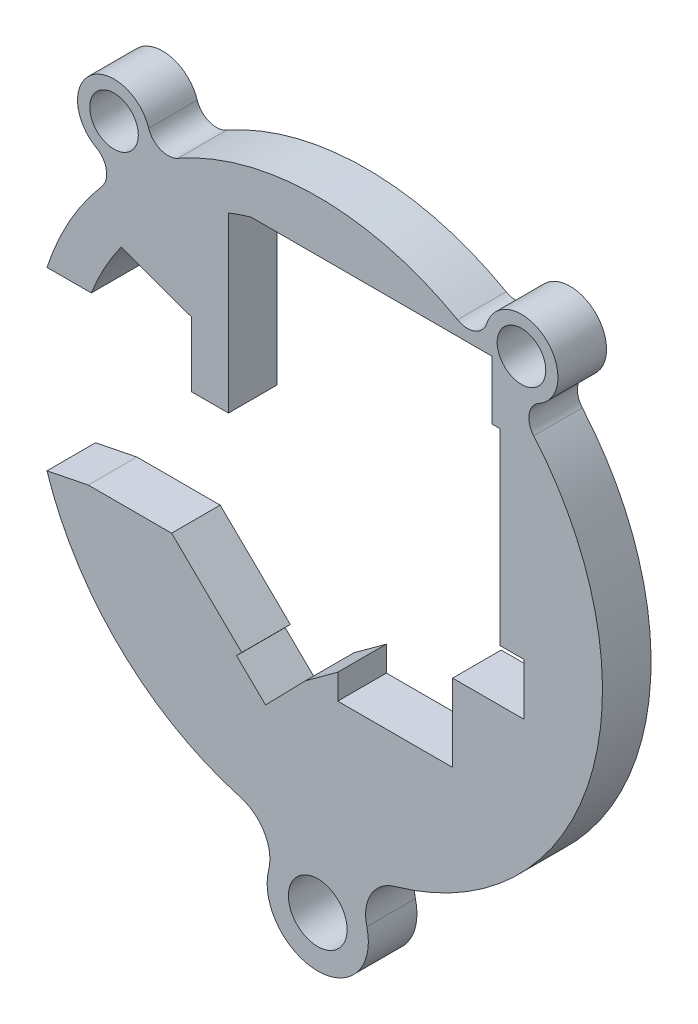
SolidWorks part; units mm, degrees
ref_plane "Front Plane" through (0, 0, 0) normal (0, 0, 1) x (1, 0, 0)
ref_plane "Top Plane" through (0, 0, 0) normal (0, 1, 0) x (1, 0, 0)
ref_plane "Right Plane" through (0, 0, 0) normal (1, 0, 0) x (0, 0, -1)
sketch "Sketch1" plane through (0, 0, 0) normal (0, 0, 1) x (1, 0, 0)
  line L1 (-14.9521, -2.9485) -> (-16.9841, -2.9485)
  line L2 (-16.9841, 2.9485) -> (-16.9841, 5.5245)
  line L3 (-14.9521, 2.9485) -> (-16.9841, 2.9485)
  line L4 (-16.9841, 5.5245) -> (-21.1739, 5.5245)
  line L5 (-16.9841, -2.9485) -> (-16.9841, -5.5245)
  line L6 (-16.9841, -5.5245) -> (-20.8712, -5.5245)
  line L7 (-15.24, 0) -> (-21.59, 0) construction
  line B0 (-15.24, 18.2372) -> (15.24, 18.2372)
  line B1 (11.43, 14.6558) -> (11.43, -0.8128)
  line B2 (0, 18.2372) -> (0, 0) construction
  line B3 (-5.6007, 14.1736) -> (-5.6007, -0.8128)
  line B4 (11.43, 14.6558) -> (-4.1791, 14.6558)
  line B5 (-5.6007, -0.8128) -> (11.43, -0.8128)
  line B6 (8.4582, -4.064) -> (12.9413, -4.064)
  line B7 (11.43, -0.8128) -> (12.9413, -0.8128)
  line B8 (12.9413, -0.8128) -> (12.9413, -4.064)
  line B9 (8.4582, -7.3406) -> (1.2573, -7.3406)
  line B10 (8.4582, -4.064) -> (8.4582, -7.3406)
  line B11 (-4.3942, -0.8128) -> (-4.3942, -4.064)
  line B12 (-4.3942, -4.064) -> (1.2573, -4.064)
  line B13 (1.2573, -4.064) -> (1.2573, -7.3406)
  line B14 (-0.7747, -8.8265) -> (-3.2737, -11.3919)
  line B15 (-0.7747, -8.8265) -> (-2.5941, -7.0541)
  line B16 (-2.5941, -7.0541) -> (-2.9176, -7.3862)
  line B17 (-2.9176, -7.3862) -> (-8.5123, -1.9362)
  line B18 (-8.5123, -1.9362) -> (-10.3645, -3.8375)
  line B19 (-10.3645, -3.8375) -> (-4.7697, -9.2875)
  line B20 (-4.7697, -9.2875) -> (-5.0932, -9.6195)
  line B21 (-5.0932, -9.6195) -> (-3.2737, -11.3919)
  line B22 (-12.3326, 18.2372) -> (-12.3326, 8.9535)
  line B23 (-7.9248, 18.2372) -> (-7.9248, 7.366) construction
  line B24 (-12.3326, 8.9535) -> (-7.9248, 7.366)
  line B25 (-5.6007, 3.302) -> (-7.9248, 3.302)
  line B26 (-7.9248, 3.302) -> (-7.9248, 7.366)
  line B27 (-14.3951, -5.0038) -> (-9.1672, -5.0038)
  line B28 (-0.7747, -8.8265) -> (1.2573, -7.3406)
  arc B29 (-3.302, 14.878) -> (3.302, 14.878) centre (0, 0) ccw
  circle B30 centre (0, -18.415) radius 1.4224
  circle B31 centre (0, 18.415) radius 1.4224
  circle B32 centre (0, 0) radius 21.59
  line B33 (1.2573, -8.9154) -> (8.4582, -8.9154)
  line B34 (1.2573, -7.3406) -> (1.2573, -8.9154)
  line B35 (8.4582, -7.3406) -> (8.4582, -8.9154)
  dimension "D1" = 2.032
  dimension "D2" = 11.049
sketch_block_instance "Block1-1"
sketch_block "Block1" parameters "D1"=3.81, "D2"=30.48, "D3"=3.5814, "D4"=9.6393, "D5"=19.05, "D6"=22.3012, "D7"=1.5113, "D8"=4.4831, "D9"=6.5278, "D10"=7.2009, "D11"=5.6515, "D12"=27.0637, "D13"=29.6291, "D14"=3.5814, "D15"=14.4653, "D16"=2.54, "D17"=2.6543, "D18"=10.3505, "D19"=9.2837, "D20"=10.8712, "D21"=7.3152, "D22"=14.9352, "D23"=23.241
extrude "Boss-Extrude1" add sketch "Sketch1" along normal blind 3.048 contours B0 B32 B29 B4 B1 B31 B30 | B27 B29 B1 B7 B8 B6 B10 B9 B28 B14 B21 B20 B19 | B3 B29 B24 B26 B25 | B0 B32 B31 | B22 B32 L4 L2 L3 B29 region at (-15.2714, -4.1381, 0) region at (-15.71, 9.7203, 0) region at (-11.7811, -5.3936, 0) region at (-7.7282, 8.9883, 0) region at (0, 21.3565, 0)
sketch "Sketch2" plane through (0, 0, 3.048) normal (0, 0, 1) x (1, 0, 0)
  line L0 (-14.3951, -5.0038) -> (-16.9841, -5.5245)
  line L2 (-16.9841, 5.5245) -> (-14.2034, 5.5245)
  line L3 (-14.3951, -5.0038) -> (-14.2034, 5.5245)
  line L4 (-16.9841, -5.5245) -> (-16.9841, 5.5245)
  arc A0 (-12.3326, 8.9535) -> (-14.9521, 2.9485) centre (0, 0) ccw construction
extrude "Cut-Extrude1" cut sketch "Sketch2" against normal through all
sketch "Sketch3" plane through (0, 0, 3.048) normal (0, 0, 1) x (1, 0, 0)
  line L0 (0, 0) -> (11.43, 14.6558) construction
  line L1 (0, 0) -> (-14.0833, 10.9835) construction
  line L2 (0, 0) -> (-10.9835, -14.0833) construction
  line L3 (0, 0) -> (14.0833, -10.9835) construction
  circle A0 centre (0, 0) radius 17.86
  circle A1 centre (0, 0) radius 21.59
extrude "Cut-Extrude2" cut sketch "Sketch3" against normal through all
sketch "Sketch4" plane through (0, 0, 3.048) normal (0, 0, 1) x (1, 0, 0)
  line L0 (0, -21.035) -> (0, 0) construction
  line L6 (10.2071, 14.6558) -> (11.43, 14.6558)
  line L7 (11.43, 14.6558) -> (11.43, 13.7235)
  line L19 (-21.6223, 17.86) -> (27.8478, 17.86) construction
  circle A0 centre (0, 0) radius 17.86
  circle A1 centre (12.7793, 15.574) radius 1.524
  circle A2 centre (-12.7793, 15.574) radius 2.286
  circle A3 centre (12.7793, 15.574) radius 2.286
  circle A4 centre (-14.5094, 12.4672) radius 1.27
  circle A5 centre (-9.3946, 16.6642) radius 1.27
  circle A6 centre (-12.7793, 15.574) radius 1.524
  circle A7 centre (0, -21.035) radius 1.8415
  circle A8 centre (0, -21.035) radius 3.175
  circle A9 centre (9.3946, 16.6642) radius 1.27
  circle A11 centre (14.5094, 12.4672) radius 1.27
  arc A12 (-1.2889, 17.8134) -> (1.2889, 17.8134) centre (0, 18.415) ccw
  arc A13 (-1.2889, 17.8134) -> (1.2889, 17.8134) centre (0, 18.415) ccw construction
  circle A14 centre (5.5404, -19.6332) radius 2.54
  circle A15 centre (-5.5404, -19.6332) radius 2.54
  arc M3 (-1.2889, -17.8134) -> (1.2889, -17.8134) centre (0, -18.415) cw
  arc M4 (1.2889, -17.8134) -> (11.43, 13.7235) centre (0, 0) ccw
  dimension "D2" = 3.048
  dimension "D4" = 2.54
  dimension "D3" = 3.683
  dimension "D1" = 4.572
  dimension "D5" = 6.35
  dimension "D6" = 5.08
extrude "Boss-Extrude3" add sketch "Sketch4" against normal blind 3.048 contours A5 A2 A0 | A2 A6 | A4 A0 A2 | A0 A12 | A9 A0 L6 A3 | L7 A3 L6 A1 | A11 A3 L7 A0 | A8 A7 | A15 A8 A0 | A14 A0 A8 M4 | A0 M3 region at (10.0871, 15.2114, 3.048) region at (10.5609, 15.4611, 3.048) region at (12.8284, 12.9196, 3.048) region at (0, 17.4932, 3.048) region at (-10.1667, 15.1037, 3.048) region at (2.6103, -18.2487, 3.048) region at (-12.8282, 12.9198, 3.048) region at (-12.5808, 13.3615, 3.048) region at (0, -17.4932, 3.048) region at (3.0615, -20.6537, 3.048) region at (-2.6103, -18.2487, 3.048)
sketch "Sketch7" plane through (0, 0, 3.048) normal (0, 0, 1) x (1, 0, 0)
  line L1 (11.43, 14.6558) -> (10.922, 14.6558)
  line L2 (11.43, 14.6558) -> (11.43, 10.9728)
  line L3 (11.43, 10.9728) -> (10.922, 10.9728)
  line L4 (10.922, 14.6558) -> (10.922, 10.9728)
  dimension "D1" = 0.508
  dimension "D2" = 3.683
extrude "Boss-Extrude4" add sketch "Sketch7" against normal up to vertex (3.048 mm away) up to point (11.43, 14.6558, 0)
